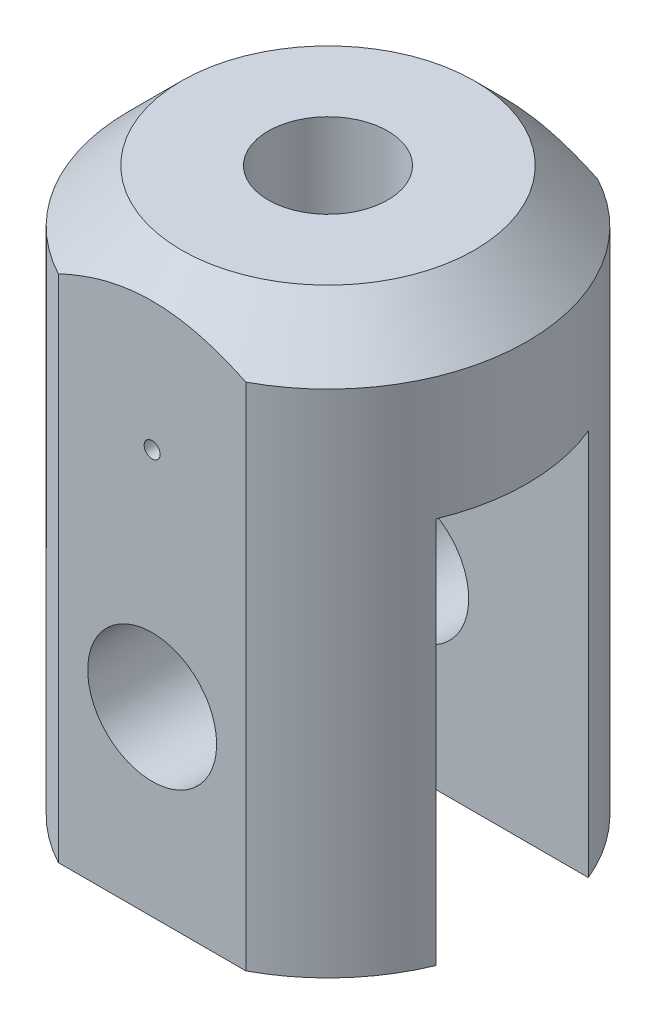
SolidWorks part; units mm, degrees
ref_plane "前视基准面" through (0, 0, 0) normal (0, 0, 1) x (1, 0, 0)
ref_plane "上视基准面" through (0, 0, 0) normal (0, 1, 0) x (1, 0, 0)
ref_plane "右视基准面" through (0, 0, 0) normal (1, 0, 0) x (0, 0, -1)
sketch "草图1" plane through (0, 0, 0) normal (0, 1, 0) x (1, 0, 0)
  line L7 (73.1341, -75) -> (-73.1341, 75) construction
  circle A2 centre (0, 0) radius 85
  dimension "D1" = 170
extrude "凸台-拉伸1" add sketch "草图1" against normal blind 240
sketch "草图2" plane through (0, 0, 0) normal (0, 1, 0) x (1, 0, 0)
  line L0 (-79.4132, 75) -> (82.5868, 75)
  line L1 (-79.4132, 75) -> (-79.4132, 89)
  line L2 (-79.4132, 89) -> (82.5868, 89)
  line L3 (82.5868, 89) -> (82.5868, 75)
  dimension "D1" = 75
  dimension "D2" = 14
  dimension "D3" = 162
extrude "切除-拉伸1" cut sketch "草图2" against normal through all
mirror "镜向1" about plane through (0, 0, 0) normal (0, 0, 1) of "切除-拉伸1"
sketch "草图3" plane through (0, 0, 0) normal (0, 0, 1) x (1, 0, 0)
  line L0 (85, -22.5) -> (62.5, 0)
  line L1 (85, -240) -> (85, 0) construction
  line L2 (85, 0) -> (40, 0) construction
  line L3 (62.5, 0) -> (85, 0)
  line L4 (85, 0) -> (85, -22.5)
  dimension "D1" = 62.5
  dimension "D2" = 22.5
revolve "切除-旋转1" cut sketch "草图3" angle 360 about axis through (0, -240, 0) along (0, 1, 0)
sketch "草图5" plane through (0, -240, 0) normal (0, -1, 0) x (1, 0, 0)
  line L1 (94, -32.5) -> (-94, -32.5)
  line L2 (94, -32.5) -> (94, 32.5)
  line L3 (94, 32.5) -> (-94, 32.5)
  line L4 (-94, -32.5) -> (-94, 32.5)
  line L5 (94, -32.5) -> (-94, 32.5) construction
  line L6 (94, 32.5) -> (-94, -32.5) construction
  point P0 (0, 0)
  dimension "D1" = 65
  dimension "D2" = 188
extrude "切除-拉伸2" cut sketch "草图5" against normal blind 165
sketch "草图6" plane through (0, 0, 75) normal (0, 0, 1) x (1, 0, 0)
  line L0 (0, 0) -> (0, -256.6173) construction
  line L1 (0, -22.5) -> (0, 0) construction
  line L2 (-40, -240) -> (40, -240) construction
  circle A0 centre (0, -162.5) radius 27.5
  circle A1 centre (0, -67.5) radius 3.4
  point P11 (0, 0)
  dimension "D1" = 55
  dimension "D3" = 6.8
  dimension "D2" = 77.5
  dimension "D4" = 95
extrude "切除-拉伸3" cut sketch "草图6" against normal through all contours A0
extrude "切除-拉伸4" cut sketch "草图6<3>" against normal blind 20 contours A1
sketch "草图6<3>" plane through (0, 0, 75) normal (0, 0, 1) x (1, 0, 0) same geometry as "草图6"
sketch "草图8" plane through (0, 0, 0) normal (0, 1, 0) x (1, 0, 0)
  circle A0 centre (0, 0) radius 25.5
  dimension "D1" = 51
extrude "切除-拉伸5" cut sketch "草图8" against normal up to next
